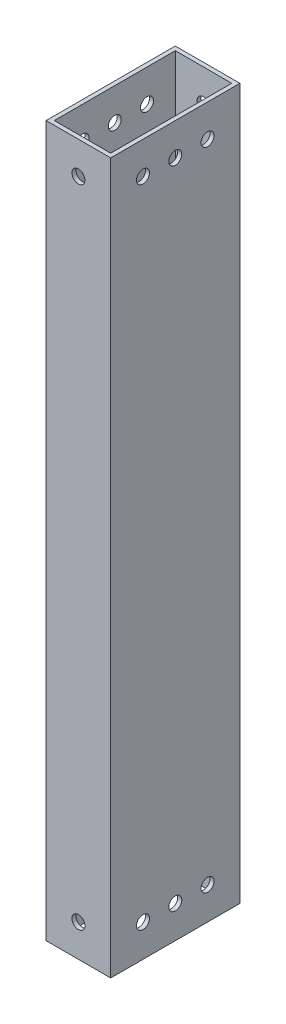
SolidWorks part; units mm, degrees
material "6061-T6 (SS)"
ref_plane "Front" through (0, 0, 0) normal (0, 0, 1) x (1, 0, 0)
ref_plane "Top" through (0, 0, 0) normal (0, 1, 0) x (1, 0, 0)
ref_plane "Right" through (0, 0, 0) normal (1, 0, 0) x (0, 0, -1)
sketch "Sketch1" plane through (0, 0, 0) normal (0, 1, 0) x (1, 0, 0)
  line L1 (12.7, 25.4) -> (-12.7, 25.4)
  line L2 (12.7, 25.4) -> (12.7, -25.4)
  line L3 (12.7, -25.4) -> (-12.7, -25.4)
  line L4 (-12.7, 25.4) -> (-12.7, -25.4)
  line L5 (12.7, 25.4) -> (-12.7, -25.4) construction
  line L6 (12.7, -25.4) -> (-12.7, 25.4) construction
  point P0 (0, 0)
  dimension "D1" = 25.4
  dimension "D2" = 50.8
extrude "Extrude-Thin1" add sketch "Sketch1" along normal up to surface (279.4 mm away) thin thin type one direction reverse wall 1.5875
sketch "Sketch4" plane through (-12.7, 0, 0) normal (-1, 0, 0) x (0, 0, 1)
  line L0 (-12.7, 12.7) -> (12.7, 12.7) construction
  line L3 (-12.7, 266.7) -> (12.7, 266.7) construction
  line L4 (-25.4, 0) -> (25.4, 0) construction
  line L5 (-25.4, 279.4) -> (25.4, 279.4) construction
  line L6 (-25.4, 279.4) -> (-25.4, 0) construction
  point P1 (-12.7, 12.7)
  point P2 (12.7, 12.7)
  point P6 (-12.7, 266.7)
  point P7 (12.7, 266.7)
  point P10 (0, 266.7)
  point P16 (-12.7, 266.7)
  point P18 (12.7, 266.7)
  point P22 (0, 12.7)
  point P26 (12.7, 12.7)
  point P28 (-12.7, 12.7)
  point P35 (0, 0)
  dimension "D1" = 12.7
  dimension "D2" = 12.7
  dimension "D3" = 12.7
hole_wizard "#10 Clearance Hole1" positions "Sketch4" profile "Sketch3" hole size "#10" standard "ANSI Inch" end condition through all
sketch "Sketch3" plane through (-12.7, 12.7, -12.7) normal (0, 1, 0) x (0, 0, 1)
  line L0 (0, 0) -> (0, 25.4)
  line L1 (0, 25.4) -> (2.5527, 25.4)
  line L2 (2.5527, 25.4) -> (2.5527, 0)
  line L5 (2.5527, 0) -> (0, 0)
  line L11 (0, -6.35) -> (0, 107.95) construction
  dimension "Thru Hole Dia." = 5.1054
  dimension "Thru Hole Depth" = 25.4
sketch "Sketch7" plane through (0, 0, 25.4) normal (0, 0, 1) x (1, 0, 0)
  line L0 (-12.7, 0) -> (12.7, 0) construction
  line L1 (-12.7, 279.4) -> (12.7, 279.4) construction
  point P0 (0, 12.7)
  point P2 (0, 266.7)
  dimension "D1" = 12.7
  dimension "D2" = 12.7
hole_wizard "#10 Clearance Hole2" positions "Sketch7" profile "Sketch6" hole size "#10" standard "ANSI Inch" end condition through all
sketch "Sketch6" plane through (0, 12.7, 25.4) normal (1, 0, 0) x (0, -1, 0)
  line L0 (0, 0) -> (0, 50.8)
  line L1 (0, 50.8) -> (2.5527, 50.8)
  line L2 (2.5527, 50.8) -> (2.5527, 0)
  line L5 (2.5527, 0) -> (0, 0)
  line L11 (0, -6.35) -> (0, 107.95) construction
  dimension "Thru Hole Dia." = 5.1054
  dimension "Thru Hole Depth" = 50.8
